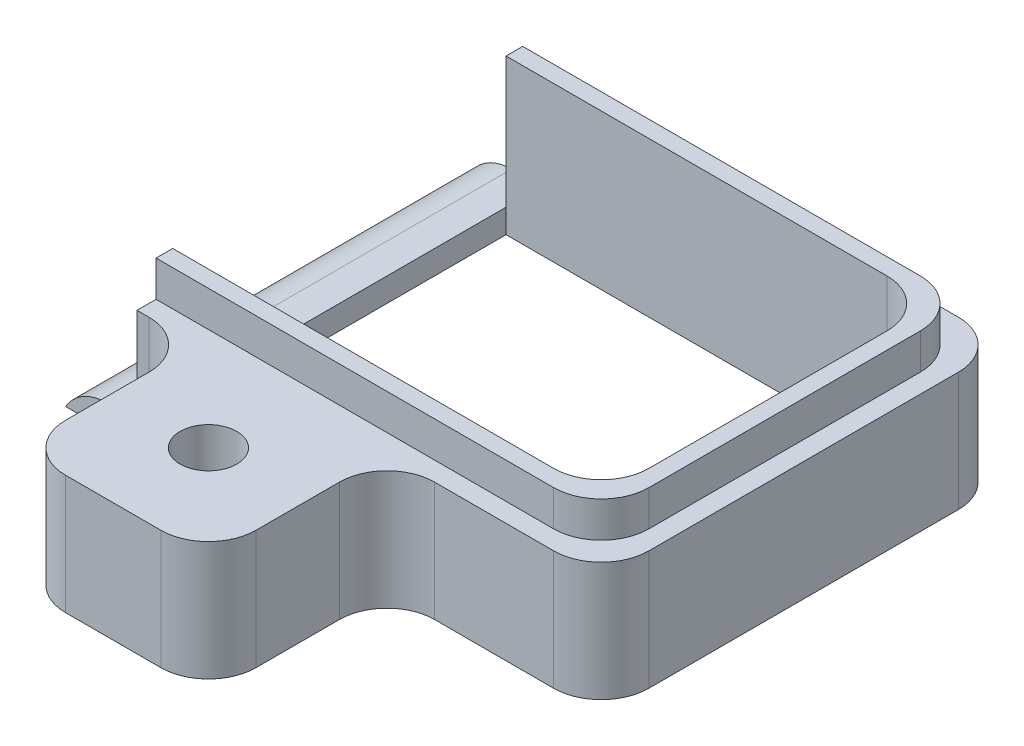
SolidWorks part; units mm, degrees
ref_plane "Front Plane" through (0, 0, 0) normal (0, 0, 1) x (1, 0, 0)
ref_plane "Top Plane" through (0, 0, 0) normal (0, 1, 0) x (1, 0, 0)
ref_plane "Right Plane" through (0, 0, 0) normal (1, 0, 0) x (0, 0, -1)
sketch "Sketch5" plane through (0, 0, 0) normal (0, 1, 0) x (1, 0, 0)
  line L1 (-5.625, -4.25) -> (5.625, -4.25)
  line L2 (-5.625, -4.25) -> (-5.625, 4.25)
  line L3 (-5.625, 4.25) -> (5.625, 4.25)
  line L4 (5.625, -4.25) -> (5.625, 4.25)
  line L5 (-5.625, -4.25) -> (5.625, 4.25) construction
  line L6 (-5.625, 4.25) -> (5.625, -4.25) construction
  point P0 (0, 0)
  dimension "D1" = 8.5
  dimension "D2" = 11.25
extrude "Extrude4" add sketch "Sketch5" along normal blind 2.5
sketch "Sketch19" plane through (0, 2.5, 0) normal (0, 1, 0) x (-1, 0, 0)
  line L0 (5.625, 4.25) -> (-5.625, 4.25) construction
  line L1 (5.625, -4.25) -> (4.125, -4.25)
  line L2 (5.625, -4.25) -> (5.625, 4.25)
  line L3 (5.625, 4.25) -> (4.125, 4.25)
  line L4 (4.125, -4.25) -> (4.125, 4.25)
  dimension "D1" = 1.5
extrude "Extrude12" cut sketch "Sketch19" against normal blind 2
sketch "Sketch21" plane through (0, 2.5, 0) normal (0, 1, 0) x (-1, 0, 0)
  line L0 (4.125, 4.25) -> (4.125, -4.25) construction
  line L1 (-4.875, -3.5) -> (4.125, -3.5)
  line L2 (-4.875, -3.5) -> (-4.875, 3.5)
  line L3 (-4.875, 3.5) -> (4.125, 3.5)
  line L4 (4.125, -3.5) -> (4.125, 3.5)
  line L5 (-5.625, -4.25) -> (4.125, -4.25) construction
  line L6 (-5.625, 4.25) -> (-5.625, -4.25) construction
  line L7 (4.125, 4.25) -> (-5.625, 4.25) construction
  dimension "D1" = 0.75
  dimension "D2" = 0.75
  dimension "D3" = 0.75
extrude "Extrude13" cut sketch "Sketch21" against normal through all
sketch "Sketch22" plane through (0, 0, 4.25) normal (0, 0, 1) x (1, 0, 0)
  line L0 (-5.625, 0) -> (5.625, 0) construction
  line L1 (-2.875, 0) -> (1.125, 0)
  line L2 (-2.875, 0) -> (-2.875, 2.5)
  line L3 (-2.875, 2.5) -> (1.125, 2.5)
  line L4 (1.125, 0) -> (1.125, 2.5)
  line L5 (-4.125, 2.5) -> (5.625, 2.5) construction
  line L6 (5.625, 2.5) -> (5.625, 0) construction
  dimension "D1" = 4
  dimension "D2" = 4.5
extrude "Extrude14" add sketch "Sketch22" along normal blind 3.75
sketch "Sketch24" plane through (0, 2.5, 0) normal (0, 1, 0) x (1, 0, 0)
  line L0 (-4.125, 3.85) -> (-4.125, 3.5)
  line L1 (-4.125, 3.5) -> (4.875, 3.5)
  line L2 (4.875, 3.5) -> (4.875, -3.5)
  line L3 (4.875, -3.5) -> (-4.125, -3.5)
  line L4 (-4.125, -3.5) -> (-4.125, -3.85)
  line L9 (-4.125, -3.85) -> (5.225, -3.85)
  line L10 (5.225, -3.85) -> (5.225, 3.85)
  line L11 (5.225, 3.85) -> (-4.125, 3.85)
  line L12 (-4.125, -3.85) -> (5.225, -3.85)
  line L13 (5.225, -3.85) -> (5.225, 3.85)
  line L14 (5.225, 3.85) -> (-4.125, 3.85)
  dimension "D1" = 0.35
extrude "Extrude15" add sketch "Sketch24" along normal blind 0.75
hole_wizard "#0-80 Tapped Hole1" positions "3DSketch1" profile "Sketch26" tap size "#0-80" standard "Ansi Inch"
sketch3d "3DSketch1"
  line L0 (1.125, 2.5, 8) -> (-2.875, 2.5, 8) construction
  line L1 (1.125, 2.5, 8) -> (1.125, 2.5, 4.25) construction
  point P0 (-0.875, 2.5, 6)
  dimension "D1" = 2
  dimension "D2" = 2
sketch "Sketch26" plane through (-0.875, 2.5, 6) normal (1, 0, 0) x (0, 0, 1)
  line L0 (0, 0) -> (0, 79.3679)
  line L1 (0, 79.3679) -> (0.5956, 79.01)
  line L2 (0.5956, 79.01) -> (0.5956, 0)
  line L5 (0.5956, 0) -> (0, 0)
  line L10 (0, 79.3679) -> (-0.5956, 79.01) construction
  line L11 (0, -6.35) -> (0, 107.95) construction
  dimension "Tap Drill Dia." = 1.1913
  dimension "Tap Drill Depth" = 79.01
  dimension "Drill Angle" = 118
fillet "Fillet4" radius 1 10 edges at (5.625, 1.25, -4.25) (5.225, 2.875, -3.85) (5.625, 1.25, 4.25) (5.225, 2.875, 3.85) (-2.875, 1.25, 8) (1.125, 1.25, 8) (4.875, 1.625, 3.5) (4.875, 1.625, -3.5)
fillet "Fillet5" radius 1 1 edges at (-5.625, 0.5, 0)
